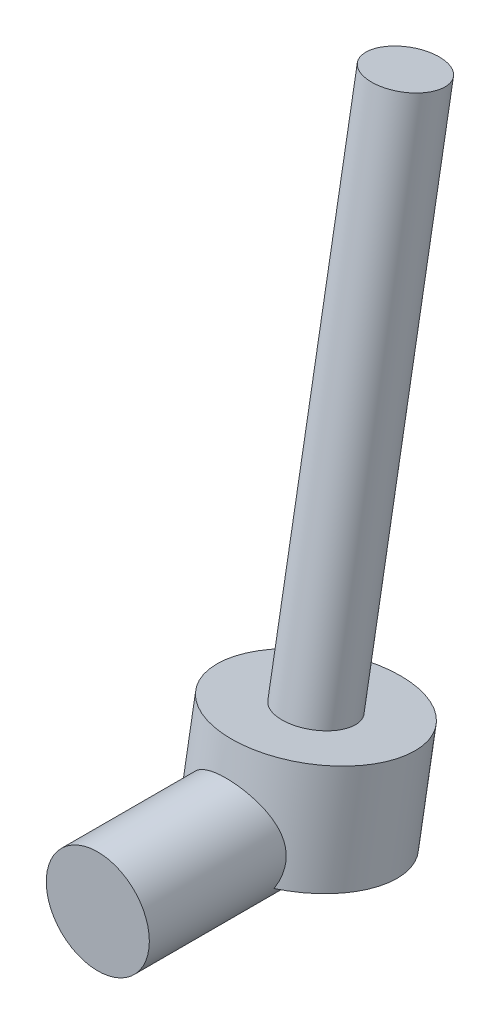
SolidWorks part; units mm, degrees
ref_plane "Front Plane" through (0, 0, 0) normal (0, 0, 1) x (1, 0, 0)
ref_plane "Top Plane" through (0, 0, 0) normal (0, 1, 0) x (1, 0, 0)
ref_plane "Right Plane" through (0, 0, 0) normal (1, 0, 0) x (0, 0, -1)
sketch "Sketch1" plane through (0, 0, 0) normal (0, 0, 1) x (1, 0, 0)
  circle A0 centre (0, 0) radius 45
  dimension "D1" = 90
extrude "Boss-Extrude1" add sketch "Sketch1" along normal blind 180 contours A0
ref_axis "Axis1" through (49.5, 0, 0) along (-1, 0, 0)
ref_plane "Plane2" through (0, 0, 0) normal (0, 0.9848, -0.1736) x (-1, 0, 0)
sketch "Sketch2" plane through (0, 0, 0) normal (0, 0.9848, -0.1736) x (-1, 0, 0)
  circle A0 centre (0, 0) radius 75
  dimension "D1" = 150
extrude "Boss-Extrude2" add sketch "Sketch2" along normal blind 60 and the other way blind 30 contours A0
sketch "Sketch3" plane through (0, 59.0885, -10.4189) normal (0, 0.9848, -0.1736) x (1, 0, 0)
  circle A0 centre (0, 0) radius 30
extrude "Boss-Extrude3" add sketch "Sketch3" along normal blind 450 contours A0
